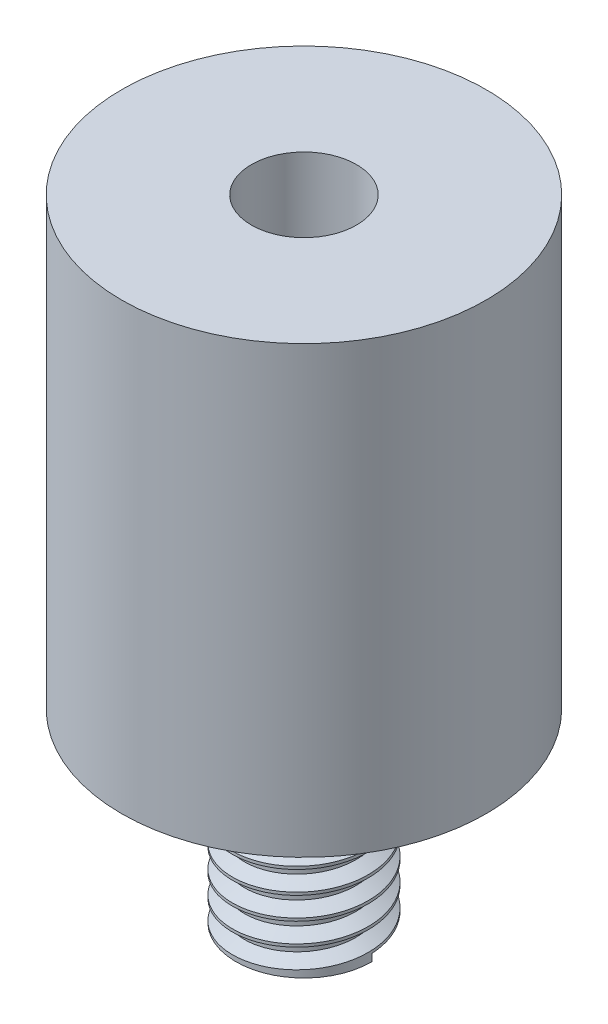
SolidWorks part; units mm, degrees
ref_plane "Front Plane" through (0, 0, 0) normal (0, 0, 1) x (1, 0, 0)
ref_plane "Top Plane" through (0, 0, 0) normal (0, 1, 0) x (1, 0, 0)
ref_plane "Right Plane" through (0, 0, 0) normal (1, 0, 0) x (0, 0, -1)
sketch "Эскиз1" plane through (0, 0, 0) normal (0, 0, 1) x (1, 0, 0)
  line L0 (0, 0) -> (0, -20.7538) construction
  line L1 (0, 0) -> (-5.5, 0)
  line L2 (-5.5, 0) -> (-5.5, 15)
  line L3 (-5.5, 15) -> (-14.75, 15)
  line L4 (-14.75, 15) -> (-14.75, 51)
  line L5 (-14.75, 51) -> (-4.25, 51)
  line L6 (-4.25, 51) -> (-4.25, 26)
  line L7 (-4.25, 26) -> (0, 26)
  line L8 (0, 26) -> (0, 0)
  dimension "D1" = 29.5
  dimension "D2" = 36
  dimension "D3" = 8.5
  dimension "D4" = 15
  dimension "D5" = 11
  dimension "D6" = 25
revolve "Повернуть1" add sketch "Эскиз1" angle 360 about L0
thread "Резьба1" pitch 1.8143 method cut profile "Профиль резьбы1" start angle 0, offset 1, length 0, pitch 1.8143, diameter 11
ref_plane "Плоскость1" through (5.5, -1, 0) normal (0, 0, 1) x (1, 0, 0)
sketch "Профиль резьбы1" plane through (5.5, -1, 0) normal (0, 0, 1) x (1, 0, 0)
  line L0 (0, 0) -> (0, 1.8143) construction
  line L11 (0, 0) -> (0, 1.5875)
  line L12 (0, 1.5875) -> (-0.982, 1.0205)
  line L13 (-0.982, 1.0205) -> (-0.982, 0.567)
  line L15 (-0.982, 0.567) -> (0, 0)
  line L17 (-0.982, 0.7937) -> (0, 0.7937) construction
  point P2 (0, 0)
  dimension "Pitch" = 1.8143
  dimension "Profile_Angle" = 60
  dimension "Profile_Land" = 0.4536
  dimension "Profile_Height" = 0.982
